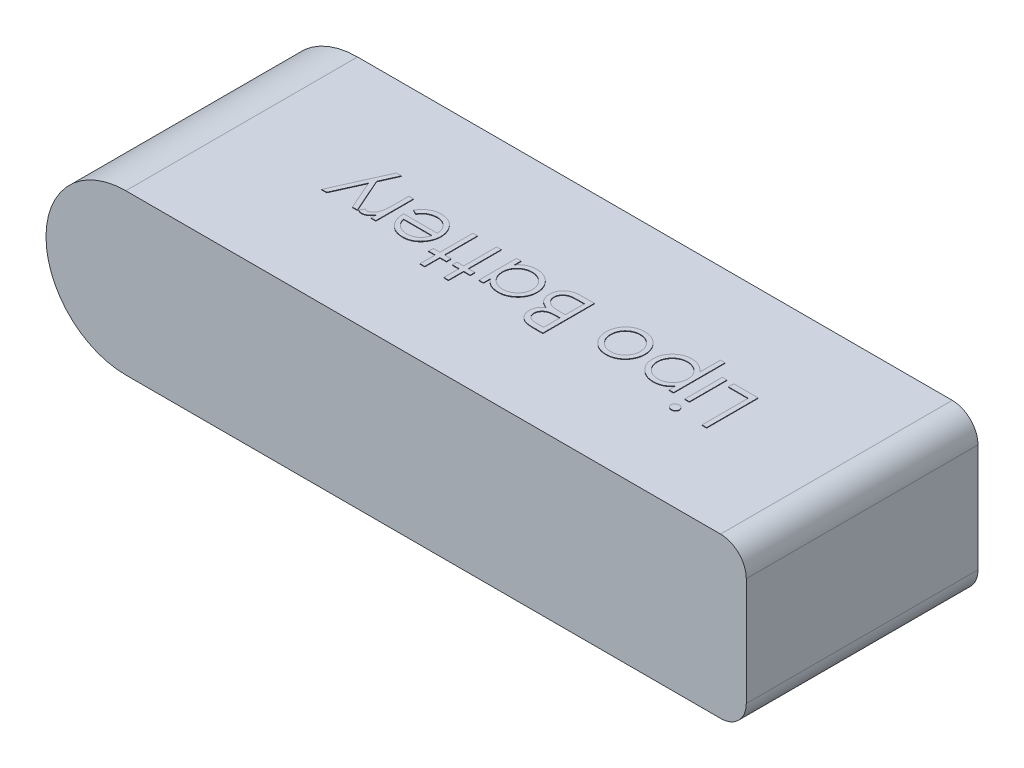
SolidWorks part; units mm, degrees
ref_plane "Front Plane" through (0, 0, 0) normal (0, 0, 1) x (1, 0, 0)
ref_plane "Top Plane" through (0, 0, 0) normal (0, 1, 0) x (1, 0, 0)
ref_plane "Right Plane" through (0, 0, 0) normal (1, 0, 0) x (0, 0, -1)
sketch "Sketch1" plane through (0, 0, 0) normal (0, 0, 1) x (1, 0, 0)
  line L0 (0, 0) -> (105, 0) construction
  line L1 (0, 15.5) -> (105, 15.5)
  line L2 (0, -15.5) -> (105, -15.5)
  line L4 (105, -15.5) -> (120.5, -15.5)
  line L5 (105, -15.5) -> (105, 15.5)
  line L6 (105, 15.5) -> (120.5, 15.5)
  line L7 (120.5, -15.5) -> (120.5, 15.5)
  arc A0 (0, 15.5) -> (0, -15.5) centre (0, 0) ccw
  arc A1 (105, -15.5) -> (105, 15.5) centre (105, 0) ccw
  point P3 (52.5, 0)
  dimension "D1" = 15.5
  dimension "D2" = 105
extrude "Boss-Extrude1" add sketch "Sketch1" along normal blind 45 contours L1 A0 L2 L5 | A1 L5 | A1 L7 L6 | A1 L4 L7 region at (46.3621, 0, 0) region at (111.5784, 0, 0) region at (117.0378, 12.0378, 0) region at (117.0378, -12.0378, 0)
fillet "Fillet1" radius 5 2 edges at (120.5, -15.5, 22.5) (120.5, 15.5, 22.5)
sketch "Sketch2" plane through (0, 15.5, 0) normal (0, 1, 0) x (-1, 0, 0)
  text T0 "Lipo Battery" font "Century Gothic" height 10
  point P1 (-87.0517, 20.501)
  point P2 (-97.6144, 18.5408)
extrude "Boss-Extrude2" add sketch "Sketch2" along normal blind 0.1
